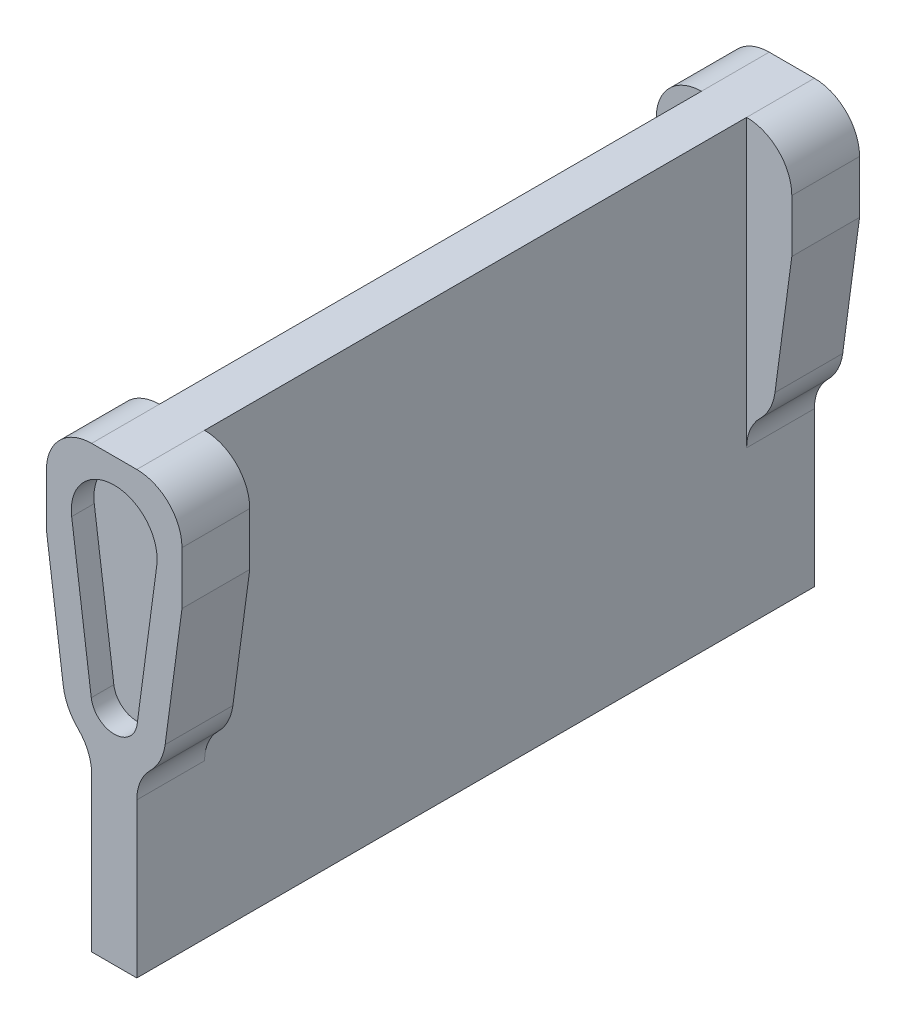
SolidWorks part; units mm, degrees
ref_plane "Front Plane" through (0, 0, 0) normal (0, 0, 1) x (1, 0, 0)
ref_plane "Top Plane" through (0, 0, 0) normal (0, 1, 0) x (1, 0, 0)
ref_plane "Right Plane" through (0, 0, 0) normal (1, 0, 0) x (0, 0, -1)
sketch "Sketch1" plane through (0, 0, 0) normal (0, 0, 1) x (1, 0, 0)
  line L0 (0, 0) -> (0, -13.25) construction
  line L1 (-1.7347, -13.4811) -> (-3.4693, -0.4623) construction
  line L2 (1.7347, -13.4811) -> (3.4693, -0.4623) construction
  circle A0 centre (0, 0) radius 3.5 construction
  circle A1 centre (0, -13.25) radius 1.75 construction
  point P7 (0, -15)
  point P10 (0, 3.5)
  dimension "D1" = 7
  dimension "D3" = 3.5
  dimension "D2" = 18.5
ref_plane "Plane2" through (0, 6, 0) normal (0, 1, 0) x (1, 0, 0)
sketch "Sketch4" plane through (0, 6, 0) normal (0, 1, 0) x (1, 0, 0)
  line L0 (-6, 30) -> (6, 30)
  line L1 (6, 30) -> (6, 24)
  line L2 (6, 24) -> (2, 24)
  line L3 (2, 24) -> (2, -24)
  line L4 (2, -24) -> (6, -24)
  line L5 (6, -24) -> (6, -30)
  line L6 (6, -30) -> (-6, -30)
  line L7 (-6, -30) -> (-6, -24)
  line L8 (-6, -24) -> (-2, -24)
  line L9 (-2, -24) -> (-2, 24)
  line L10 (-2, 24) -> (-6, 24)
  line L11 (-6, 24) -> (-6, 30)
  point P12 (-2, 0)
  point P14 (0, 30)
  dimension "D1" = 6
  dimension "D2" = 60
  dimension "D3" = 6
  dimension "D4" = 4
extrude "Boss-Extrude2" add sketch "Sketch4" against normal blind 39
sketch "Sketch5" plane through (0, 0, 30) normal (0, 0, 1) x (1, 0, 0)
  line L0 (3.7667, -0.5019) -> (2.032, -13.5208)
  line L9 (-3.7667, -0.5019) -> (-2.032, -13.5208)
  arc A9 (3.7667, -0.5019) -> (-3.7667, -0.5019) centre (0, 0) ccw
  circle A10 centre (0, 0) radius 3.5 construction
  arc A11 (-2.032, -13.5208) -> (2.032, -13.5208) centre (0, -13.25) ccw
  circle A12 centre (0, -13.25) radius 1.75 construction
  dimension "D1" = 0.3
  dimension "D2" = 0.3
extrude "Cut-Extrude1" cut sketch "Sketch5" against normal blind 2
mirror "Mirror1" about plane through (0, 0, 0) normal (0, 0, 1) of "Cut-Extrude1"
fillet "Fillet1" radius 4 4 edges at (-6, 6, -27) (6, 6, -27) (6, 6, 27) (-6, 6, 27)
sketch "Sketch8" plane through (0, 0, 0) normal (0, 0, 1) x (1, 0, 0)
  line L6 (-6, -33) -> (-6, 2) construction
  line L7 (6, -33) -> (6, 2) construction
  line L8 (4.5101, -13.8509) -> (6.2448, -0.8321)
  line L9 (-6.2448, -0.8321) -> (-4.5101, -13.8509)
  line L10 (4.5101, -13.8509) -> (6, -2.6694)
  line L11 (-6, -2.6694) -> (-4.5101, -13.8509)
  line L12 (-2, -33) -> (-2, -19.3412)
  line L14 (2, -33) -> (2, -19.3412)
  line L16 (-6, -2.6694) -> (-6, -33)
  line L17 (-6, -33) -> (-2, -33)
  line L18 (6, -2.6694) -> (6, -33)
  line L19 (6, -33) -> (2, -33)
  arc A2 (3.193, -16.4915) -> (4.5101, -13.8509) centre (0, -13.25) ccw
  arc A3 (-4.5101, -13.8509) -> (4.5101, -13.8509) centre (0, -13.25) ccw
  arc A4 (-4.5101, -13.8509) -> (-3.193, -16.4915) centre (0, -13.25) ccw
  arc A5 (-2, -19.3412) -> (-3.193, -16.4915) centre (-6, -19.3412) ccw
  arc A6 (2, -19.3412) -> (3.193, -16.4915) centre (6, -19.3412) cw
  point P14 (2, -17.3369)
  dimension "D2" = 4
  dimension "D3" = 4
  dimension "D1" = 2.5
extrude "Cut-Extrude3" cut sketch "Sketch8" against normal through all both and the other way through all
sketch "Sketch10" plane through (0, 0, 0) normal (0, 0, 1) x (1, 0, 0)
  line L0 (-2, -33) -> (-2, -30.5793)
  line L1 (-2, -33) -> (-2, -19.3412) construction
  line L2 (-2, -30.5793) -> (-5.5, -32.6)
  line L3 (-5.5, -33) -> (-2, -33)
  line L4 (-5.5, -33) -> (-5.5, -32.6)
  dimension "D1" = 30
  dimension "D2" = 0.4
  dimension "D3" = 3.5
extrude "Boss-Extrude3" add sketch "Sketch10" along normal mid plane 44
fillet "Fillet3" radius 2 1 edges at (-2, -30.5793, 0)
